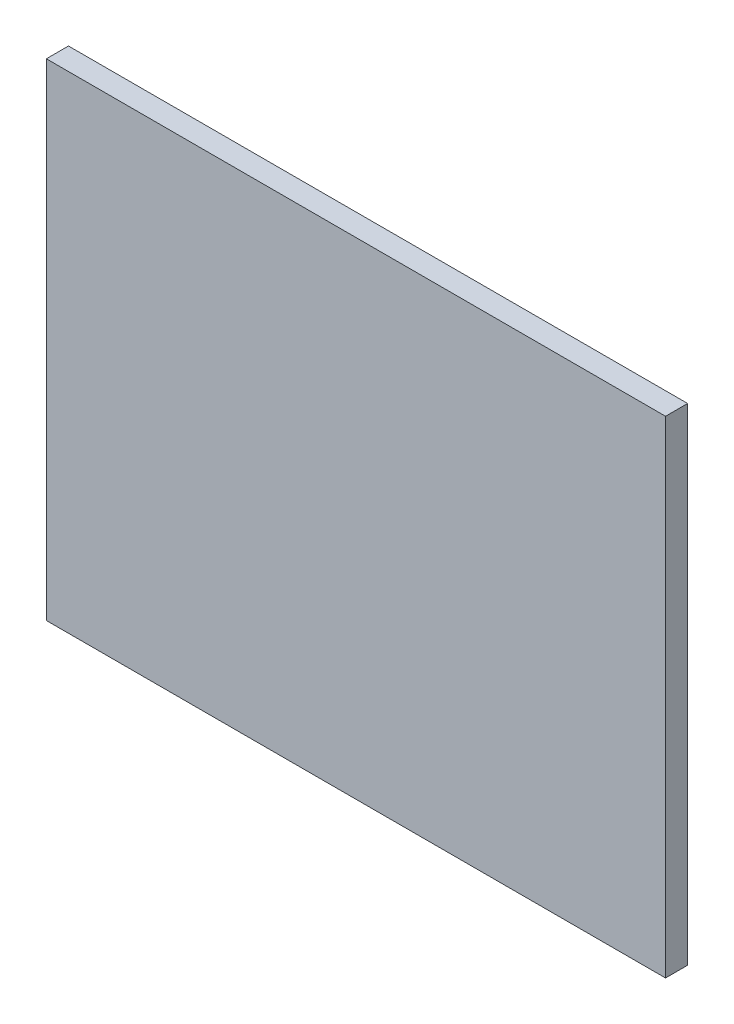
SolidWorks part; units mm, degrees
ref_plane "Piano frontale" through (0, 0, 0) normal (0, 0, 1) x (1, 0, 0)
ref_plane "Piano superiore" through (0, 0, 0) normal (0, 1, 0) x (1, 0, 0)
ref_plane "Piano destro" through (0, 0, 0) normal (1, 0, 0) x (0, 0, -1)
sketch "Schizzo1" plane through (0, 0, 0) normal (0, 0, 1) x (1, 0, 0)
  line L1 (0, 0) -> (56, 0)
  line L2 (0, 0) -> (0, 44)
  line L3 (0, 44) -> (56, 44)
  line L4 (56, 0) -> (56, 44)
  dimension "D1" = 44
  dimension "D2" = 56
extrude "Estrusione-Estrusione1" add sketch "Schizzo1" along normal blind 2
